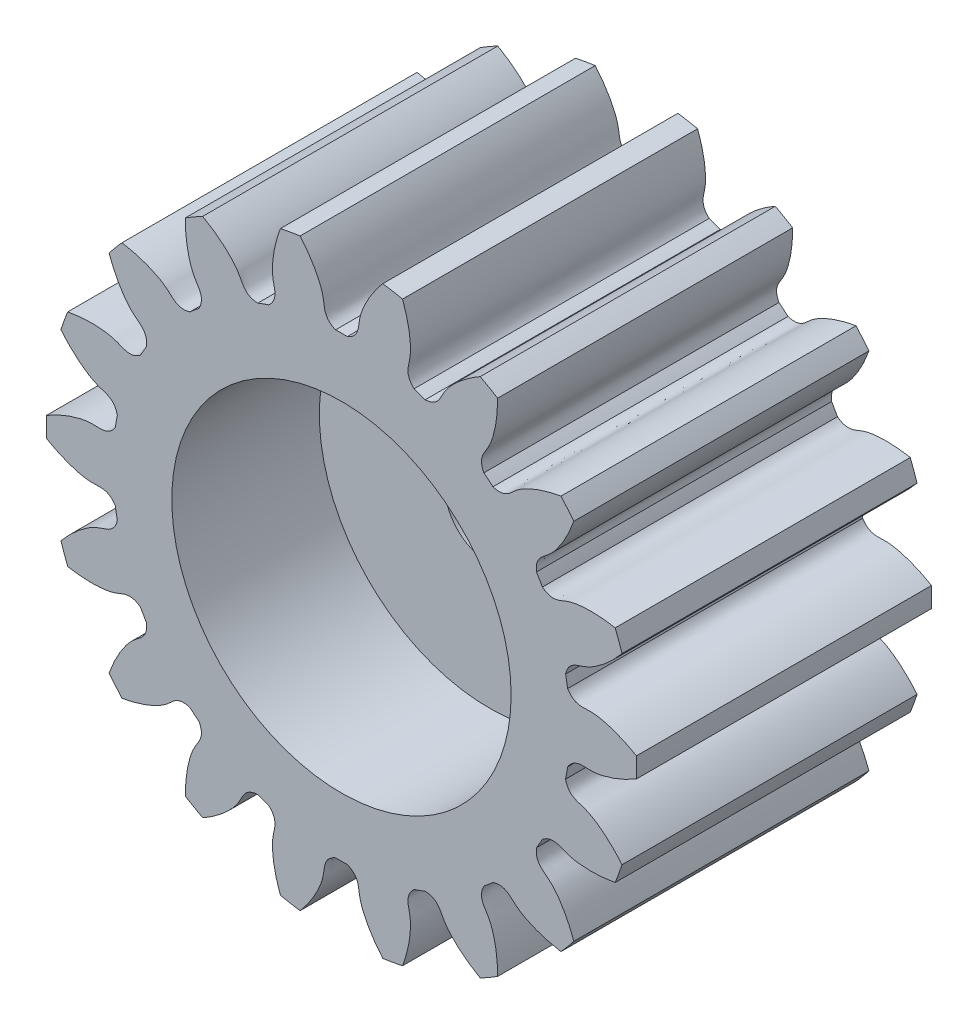
SolidWorks part; units mm, degrees
ref_plane "前视基准面" through (0, 0, 0) normal (0, 0, 1) x (1, 0, 0)
ref_plane "上视基准面" through (0, 0, 0) normal (0, 1, 0) x (1, 0, 0)
ref_plane "右视基准面" through (0, 0, 0) normal (1, 0, 0) x (0, 0, -1)
other "Configuration Table"
sketch "草图1" plane through (0, 0, 0) normal (0, 0, 1) x (1, 0, 0)
  circle A0 centre (0, 0) radius 10
extrude "凸台-拉伸1" add sketch "草图1" along normal blind 10
ref_axis "基准轴1" through (0, 0, -0.5) along (0, 0, 1)
sketch "草图2" plane through (0, 0, 0) normal (0, 0, 1) x (1, 0, 0)
  line L0 (0, 0) -> (0, 10) construction
  circle A0 centre (0, 0) radius 10 construction
  arc A1 (0.1994, 7.7474) -> (-0.1994, 7.7474) centre (0, 0) ccw
  arc A2 (3.0986, 11.3067) -> (-3.0986, 11.3067) centre (0, 0) ccw
  spline S0 degree 3 poles (0.1994, 7.7474) (0.6151, 7.9187) (0.5628, 8.2387) (0.6318, 8.5426) (0.6388, 8.5705) (0.6471, 8.6015) (0.657, 8.6357) (0.6686, 8.6728) (0.682, 8.7129) (0.6974, 8.7559) (0.7148, 8.8018) (0.7344, 8.8504) (0.7563, 8.9018) (0.7806, 8.9557) (0.8074, 9.0123) (0.8368, 9.0713) (0.869, 9.1328) (0.9041, 9.1965) (0.9421, 9.2625) (0.9831, 9.3305) (1.0273, 9.4006) (1.0748, 9.4727) (1.1256, 9.5465) (1.1799, 9.6221) (1.2377, 9.6993) (1.2991, 9.778) (1.3642, 9.858) (1.433, 9.9394) (1.5057, 10.0218) (1.5824, 10.1053) (1.663, 10.1897) (1.7477, 10.2749) (1.8365, 10.3607) (1.9295, 10.447) (2.0267, 10.5337) (2.1282, 10.6206) (2.234, 10.7076) (2.3442, 10.7946) (2.4588, 10.8814) (2.5779, 10.9679) (2.7015, 11.0539) (2.8741, 11.169) (3.0076, 11.2523) (3.0986, 11.3067) knots 0 0 0 0 0.187592 0.192996 0.199121 0.205966 0.213531 0.221818 0.230824 0.240552 0.250999 0.262168 0.274057 0.286666 0.299996 0.314047 0.328818 0.344309 0.360521 0.377454 0.395107 0.413481 0.432575 0.45239 0.472926 0.494181 0.516158 0.538855 0.562272 0.58641 0.611269 0.636848 0.663148 0.690168 0.717909 0.74637 0.775552 0.805454 0.836077 0.867421 0.899485 0.932269 1 1 1 1
  spline S1 degree 3 poles (-0.1994, 7.7474) (-0.6151, 7.9187) (-0.5628, 8.2387) (-0.6318, 8.5426) (-0.6388, 8.5705) (-0.6471, 8.6015) (-0.657, 8.6357) (-0.6686, 8.6728) (-0.682, 8.7129) (-0.6974, 8.7559) (-0.7148, 8.8018) (-0.7344, 8.8504) (-0.7563, 8.9018) (-0.7806, 8.9557) (-0.8074, 9.0123) (-0.8368, 9.0713) (-0.869, 9.1328) (-0.9041, 9.1965) (-0.9421, 9.2625) (-0.9831, 9.3305) (-1.0273, 9.4006) (-1.0748, 9.4727) (-1.1256, 9.5465) (-1.1799, 9.6221) (-1.2377, 9.6993) (-1.2991, 9.778) (-1.3642, 9.858) (-1.433, 9.9394) (-1.5057, 10.0218) (-1.5824, 10.1053) (-1.663, 10.1897) (-1.7477, 10.2749) (-1.8365, 10.3607) (-1.9295, 10.447) (-2.0267, 10.5337) (-2.1282, 10.6206) (-2.234, 10.7076) (-2.3442, 10.7946) (-2.4588, 10.8814) (-2.5779, 10.9679) (-2.7015, 11.0539) (-2.8741, 11.169) (-3.0076, 11.2523) (-3.0986, 11.3067) knots 0 0 0 0 0.187592 0.192996 0.199121 0.205966 0.213531 0.221818 0.230824 0.240552 0.250999 0.262168 0.274057 0.286666 0.299996 0.314047 0.328818 0.344309 0.360521 0.377454 0.395107 0.413481 0.432575 0.45239 0.472926 0.494181 0.516158 0.538855 0.562272 0.58641 0.611269 0.636848 0.663148 0.690168 0.717909 0.74637 0.775552 0.805454 0.836077 0.867421 0.899485 0.932269 1 1 1 1
extrude "切除-拉伸1" cut sketch "草图2" along normal through all
pattern_circular "阵列(圆周)1" count 18 every 20 about axis through (0, 0, -0.5) along (0, 0, 1) of "切除-拉伸1"
sketch "草图3" plane through (0, 0, 0) normal (0, 0, 1) x (1, 0, 0)
  circle A0 centre (0, 0) radius 9 construction
  dimension "Dn" = 18
sketch "草图4" plane through (0, 0, 10) normal (0, 0, 1) x (1, 0, 0)
  circle A0 centre (0, 0) radius 5.75
  dimension "D1" = 11.5
extrude "切除-拉伸2" cut sketch "草图4" against normal blind 5
sketch "草图5" plane through (0, 0, 5) normal (0, 0, 1) x (1, 0, 0)
  circle A0 centre (0, 0) radius 1.5
  dimension "D1" = 3
extrude "切除-拉伸3" cut sketch "草图5" against normal up to surface (5 mm away) up to face at (0, 0, 0)
